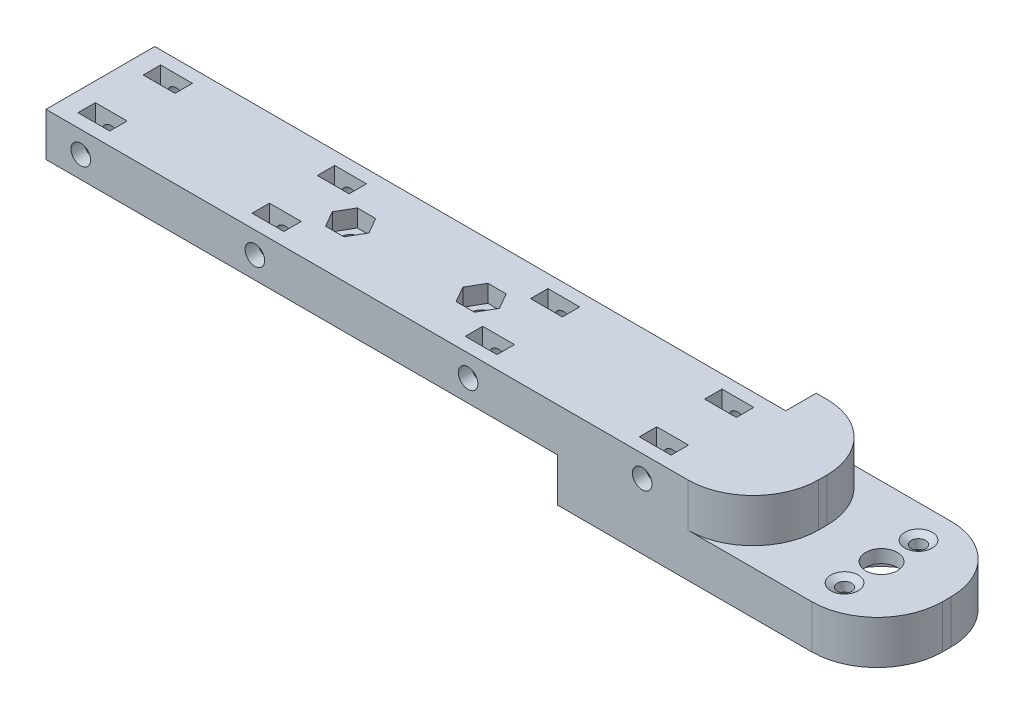
SolidWorks part; units mm, degrees
ref_plane "Front Plane" through (0, 0, 0) normal (0, 0, 1) x (1, 0, 0)
ref_plane "Top Plane" through (0, 0, 0) normal (0, 1, 0) x (1, 0, 0)
ref_plane "Right Plane" through (0, 0, 0) normal (1, 0, 0) x (0, 0, -1)
sketch "Sketch1" plane through (0, 0, 0) normal (0, 1, 0) x (1, 0, 0)
  line L7 (0, 0) -> (145, 0)
  line L8 (0, 0) -> (0, 25)
  line L9 (0, 25) -> (145, 25)
  line L10 (145, 0) -> (145, 25)
  dimension "D1" = 25
  dimension "D3" = 145
extrude "Boss-Extrude1" add sketch "Sketch1" along normal blind 10 contours L7 L10 L9 region at (72.5, 0, -12.5)
sketch "Sketch2" plane through (0, 10, 0) normal (0, 1, 0) x (1, 0, 0)
  line L5 (145, 0) -> (162.5, 0)
  line L6 (145, 0) -> (145, 32)
  line L7 (145, 32) -> (162.5, 32)
  line L8 (162.5, 0) -> (162.5, 32)
  dimension "D1" = 17.5
  dimension "D2" = 32
extrude "Boss-Extrude2" add sketch "Sketch2" against normal blind 10
sketch "Sketch4" plane through (0, 0, 0) normal (0, -1, 0) x (1, 0, 0)
  line L0 (162.5, -32) -> (191, -32) construction
  line L1 (162.5, 0) -> (117.5, 0) construction
  line L2 (0, 0) -> (162.5, 0) construction
  line L4 (117.5, 0) -> (191, 0)
  line L5 (117.5, 0) -> (117.5, -32)
  line L6 (117.5, -32) -> (191, -32)
  line L7 (191, 0) -> (191, -32)
  dimension "D1" = 28.5
  dimension "D2" = 45
extrude "Boss-Extrude3" add sketch "Sketch4" along normal blind 10
sketch "Sketch8" plane through (0, 0, -25) normal (0, 0, -1) x (-1, 0, 0)
  line L0 (-145, 5) -> (0, 5) construction
  line L1 (-145, 10) -> (-145, 0) construction
  line L2 (0, 10) -> (0, 0) construction
  line L3 (-72.5, 10) -> (-72.5, 0) construction
  line L4 (0, 10) -> (-145, 10) construction
  line L5 (0, 0) -> (-117.5, 0) construction
  circle A0 centre (-137, 5) radius 2.25
  circle A1 centre (-97, 5) radius 2.25
  circle A2 centre (-48, 5) radius 2.25
  circle A3 centre (-8, 5) radius 2.25
  dimension "D1" = 8
  dimension "D2" = 4.5
  dimension "D4" = 40
  dimension "D3" = 2
extrude "Cut-Extrude5" cut sketch "Sketch8" against normal through all
sketch "Sketch9" plane through (0, 10, 0) normal (0, 1, 0) x (1, 0, 0)
  line L0 (145, 25) -> (145, 0) construction
  line L1 (0, 0) -> (162.5, 0) construction
  line L2 (145, 12.5) -> (0, 12.5) construction
  line L3 (0, 0) -> (0, 25) construction
  line L4 (72.5, 25) -> (72.5, 0) construction
  line L5 (0, 25) -> (145, 25) construction
  line L6 (137, 0) -> (137, 25) construction
  line L7 (140.65, 22) -> (133.35, 22)
  line L8 (140.65, 7) -> (133.35, 7)
  line L9 (140.65, 7) -> (140.65, 3)
  line L10 (140.65, 3) -> (133.35, 3)
  line L11 (133.35, 7) -> (133.35, 3)
  line L12 (140.65, 7) -> (133.35, 3) construction
  line L13 (140.65, 3) -> (133.35, 7) construction
  line L14 (133.35, 18) -> (133.35, 22)
  line L15 (140.65, 18) -> (133.35, 18)
  line L16 (140.65, 18) -> (140.65, 22)
  line L17 (100.65, 7) -> (100.65, 3)
  line L18 (100.65, 7) -> (93.35, 7)
  line L19 (93.35, 7) -> (93.35, 3)
  line L20 (100.65, 3) -> (93.35, 3)
  line L21 (100.65, 22) -> (93.35, 22)
  line L22 (93.35, 18) -> (93.35, 22)
  line L23 (100.65, 18) -> (93.35, 18)
  line L24 (100.65, 18) -> (100.65, 22)
  line L25 (4.35, 18) -> (4.35, 22)
  line L26 (4.35, 18) -> (11.65, 18)
  line L27 (11.65, 18) -> (11.65, 22)
  line L28 (4.35, 22) -> (11.65, 22)
  line L29 (44.35, 18) -> (44.35, 22)
  line L30 (44.35, 18) -> (51.65, 18)
  line L31 (51.65, 18) -> (51.65, 22)
  line L32 (44.35, 22) -> (51.65, 22)
  line L33 (44.35, 7) -> (51.65, 7)
  line L34 (51.65, 7) -> (51.65, 3)
  line L35 (44.35, 3) -> (51.65, 3)
  line L36 (44.35, 7) -> (44.35, 3)
  line L37 (4.35, 3) -> (11.65, 3)
  line L38 (11.65, 7) -> (11.65, 3)
  line L39 (4.35, 7) -> (11.65, 7)
  line L40 (4.35, 7) -> (4.35, 3)
  point P15 (137, 5)
  dimension "D1" = 8
  dimension "D2" = 5
  dimension "D3" = 7.3
  dimension "D4" = 4
  dimension "D6" = 40
  dimension "D5" = 2
extrude "Cut-Extrude6" cut sketch "Sketch9" against normal up to surface (10 mm away) up to face at (58.75, 0, -12.5)
sketch "Sketch10" plane through (0, 0, 0) normal (0, 1, 0) x (1, 0, 0)
  line L0 (191, 16) -> (162.5, 16) construction
  line L1 (191, 32) -> (191, 0) construction
  line L2 (162.5, 0) -> (162.5, 32) construction
  circle A0 centre (176, 16) radius 3.65
  dimension "D1" = 15
  dimension "D2" = 7.3
extrude "Cut-Extrude7" cut sketch "Sketch10" against normal up to next
sketch "Sketch11" plane through (0, -10, 0) normal (0, -1, 0) x (1, 0, 0)
  circle A0 centre (176, -16) radius 12.75
  dimension "D1" = 25.5
extrude "Cut-Extrude8" cut sketch "Sketch11" against normal blind 7
sketch "Sketch14" plane through (0, -3, 0) normal (0, -1, 0) x (1, 0, 0)
  line L0 (176, -16) -> (176, -3.25) construction
  line L1 (163.25, -16) -> (188.75, -16) construction
  circle A0 centre (176, -16) radius 12.75 construction
  circle A1 centre (176, -7.5) radius 1.65
  circle A2 centre (176, -16) radius 12.75 construction
  circle A3 centre (176, -24.5) radius 1.65
  dimension "D1" = 3.3
  dimension "D2" = 8.5
extrude "Cut-Extrude11" cut sketch "Sketch14" against normal up to next
chamfer "Chamfer1" distance 1.5 angle 30 2 edges at (176, 0, -26.15) (176, 0, -9.15) first distance on face at (176, 0, -9.15)
fillet "Fillet1" radius 15 4 edges at (162.5, 5, 0) (162.5, 5, -32) (191, -5, -32) (191, -5, 0)
sketch "Sketch15" plane through (0, 10, 0) normal (0, 1, 0) x (1, 0, 0)
  line L0 (0, 12.5) -> (162.2902, 12.5) construction
  line L1 (0, 0) -> (0, 25) construction
  arc A0 (147.5, 0) -> (162.5, 15) centre (147.5, 15) ccw construction
  circle A1 centre (57.5, 12.5) radius 2.25
  circle A2 centre (87.5, 12.5) radius 2.25
  dimension "D1" = 57.5
  dimension "D2" = 4.5
  dimension "D4" = 30
  dimension "D3" = 2
extrude "Cut-Extrude12" cut sketch "Sketch15" against normal through all
sketch "Sketch16" plane through (0, 10, 0) normal (0, 1, 0) x (1, 0, 0)
  line L0 (91.7147, 12.5) -> (89.6073, 16.15)
  line L1 (61.7147, 12.5) -> (59.6073, 16.15)
  line L2 (59.6073, 16.15) -> (55.3927, 16.15)
  line L3 (55.3927, 16.15) -> (53.2853, 12.5)
  line L4 (53.2853, 12.5) -> (55.3927, 8.85)
  line L5 (55.3927, 8.85) -> (59.6073, 8.85)
  line L6 (59.6073, 8.85) -> (61.7147, 12.5)
  line L7 (89.6073, 16.15) -> (85.3927, 16.15)
  line L8 (85.3927, 16.15) -> (83.2853, 12.5)
  line L9 (83.2853, 12.5) -> (85.3927, 8.85)
  line L10 (85.3927, 8.85) -> (89.6073, 8.85)
  line L11 (89.6073, 8.85) -> (91.7147, 12.5)
  circle A0 centre (57.5, 12.5) radius 3.65 construction
  dimension "D1" = 7.3
  dimension "D2" = 3.65
  dimension "D4" = 30
  dimension "D3" = 2
extrude "Cut-Extrude13" cut sketch "Sketch16" against normal blind 4
